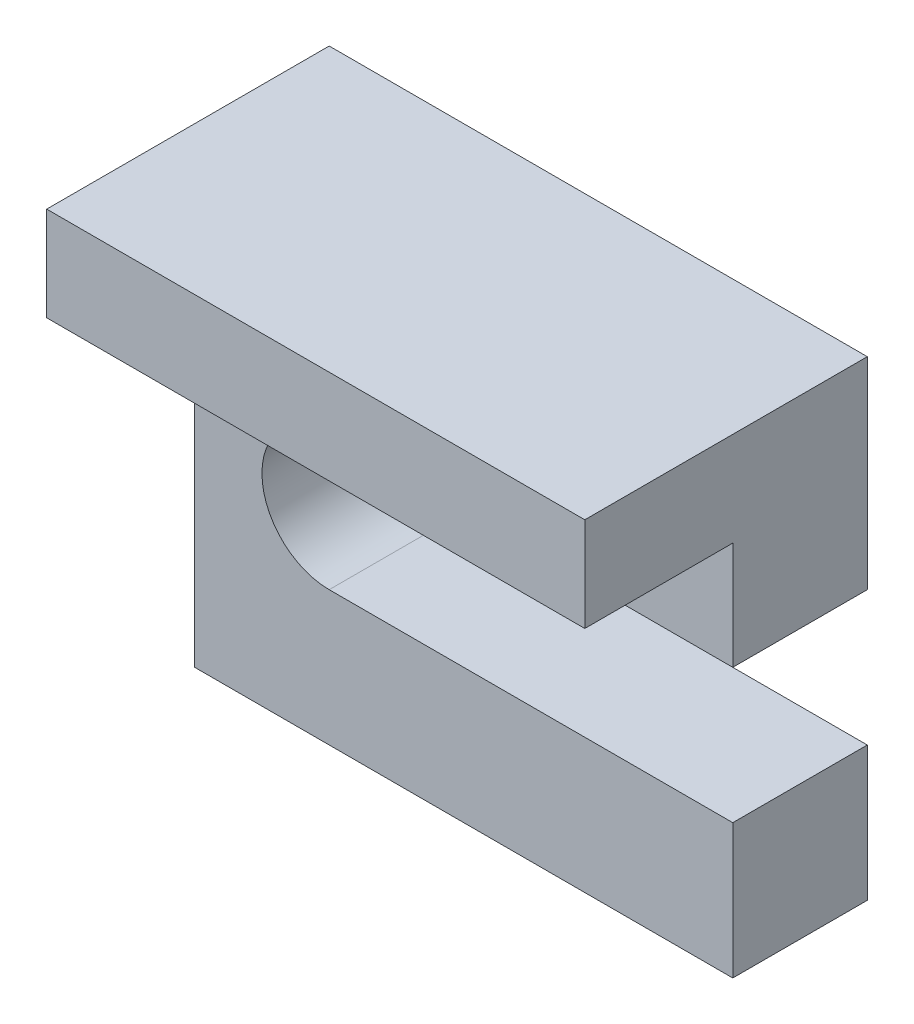
SolidWorks part; units mm, degrees
ref_plane "Front Plane" through (0, 0, 0) normal (0, 0, 1) x (1, 0, 0)
ref_plane "Top Plane" through (0, 0, 0) normal (0, 1, 0) x (1, 0, 0)
ref_plane "Right Plane" through (0, 0, 0) normal (1, 0, 0) x (0, 0, -1)
sketch "Sketch1" plane through (0, 0, 0) normal (1, 0, 0) x (0, 0, -1)
  line L0 (-16, 17.5) -> (5, 17.5)
  line L1 (5, 17.5) -> (5, -17.5)
  line L2 (5, -17.5) -> (-5, -17.5)
  line L3 (-5, -17.5) -> (-5, 10.5)
  line L4 (-5, 10.5) -> (-16, 10.5)
  line L5 (-16, 10.5) -> (-16, 17.5)
  line L6 (-5, -17.5) -> (5, 17.5) construction
  dimension "D1" = 7
  dimension "D2" = 10
  dimension "D3" = 11
  dimension "D4" = 35
extrude "Boss-Extrude1" add sketch "Sketch1" along normal blind 20 and the other way blind 20
sketch "Sketch2" plane through (0, 0, 0) normal (0, 0, 1) x (1, 0, 0)
  line L0 (-10, 2.5) -> (20, 2.5)
  line L1 (20, 10.5) -> (20, -17.5) construction
  line L2 (20, 2.5) -> (20, -7.5)
  line L3 (20, -7.5) -> (-10, -7.5)
  line L4 (-15, -2.5) -> (20, -2.5) construction
  line L5 (-20, -17.5) -> (20, -17.5) construction
  circle A0 centre (-10, -2.5) radius 5
  dimension "D1" = 10
  dimension "D2" = 35
  dimension "D3" = 10
extrude "Cut-Extrude1" cut sketch "Sketch2" against normal through all both and the other way through all contours A0 L4 | A0 L4 L2 L0 | L4 A0 L3 L2 | L4 A0 region at (6.9396, 0.0569, 0) region at (-10, -0.3779, 0) region at (-10, -4.6221, 0) region at (6.9396, -5.0569, 0)
